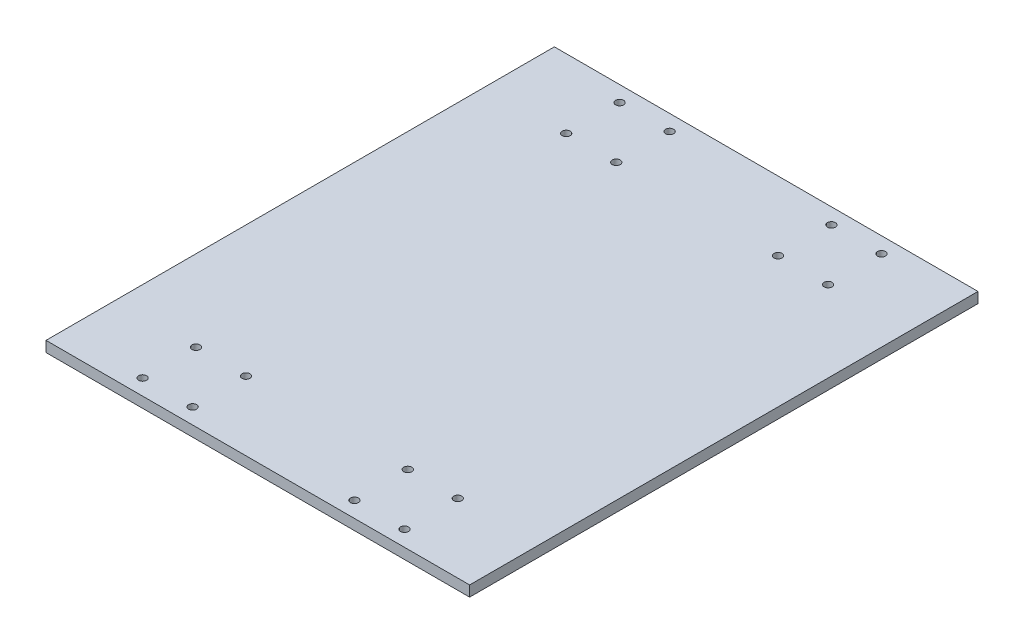
SolidWorks part; units mm, degrees
ref_plane "Front Plane" through (0, 0, 0) normal (0, 0, 1) x (1, 0, 0)
ref_plane "Top Plane" through (0, 0, 0) normal (0, 1, 0) x (1, 0, 0)
ref_plane "Right Plane" through (0, 0, 0) normal (1, 0, 0) x (0, 0, -1)
sketch "Sketch2" plane through (0, 0, 0) normal (0, 1, 0) x (1, 0, 0)
  line L1 (-127, 152.4) -> (127, 152.4)
  line L2 (-127, 152.4) -> (-127, -152.4)
  line L3 (-127, -152.4) -> (127, -152.4)
  line L4 (127, 152.4) -> (127, -152.4)
  line L5 (-127, 152.4) -> (127, -152.4) construction
  line L6 (-127, -152.4) -> (127, 152.4) construction
  point P0 (0, 0)
  dimension "D1" = 304.8
  dimension "D2" = 254
extrude "Boss-Extrude1" add sketch "Sketch2" along normal blind 6.35
ref_plane "Top" through (0, 0, -152.4) normal (0, 0, -1) x (-1, 0, 0)
hole_wizard "M4 Clearance Hole1" positions "Sketch4" profile "Sketch5" hole size "M4" standard "ANSI Metric" end condition up to next
sketch "Sketch4" plane through (0, 6.35, 0) normal (0, 1, 0) x (1, 0, 0)
  circle A0 centre (78.5, -111) radius 2.5 construction
  circle A1 centre (48.5, -111) radius 2.5 construction
  circle A2 centre (48.5, -143) radius 2.5 construction
  circle A3 centre (78.5, -143) radius 2.5 construction
  circle A4 centre (-48.5, -111) radius 2.5 construction
  circle A5 centre (-48.5, -143) radius 2.5 construction
  circle A6 centre (-78.5, -111) radius 2.5 construction
  circle A7 centre (-78.5, -143) radius 2.5 construction
  circle A8 centre (78.5, 143) radius 2.5 construction
  circle A9 centre (78.5, 111) radius 2.5 construction
  circle A10 centre (48.5, 143) radius 2.5 construction
  circle A11 centre (48.5, 111) radius 2.5 construction
  circle A12 centre (-48.5, 143) radius 2.5 construction
  circle A13 centre (-48.5, 111) radius 2.5 construction
  circle A14 centre (-78.5, 143) radius 2.5 construction
  circle A15 centre (-78.5, 111) radius 2.5 construction
  circle A16 centre (78.5, -111) radius 2.5 construction
  circle A17 centre (48.5, -111) radius 2.5 construction
  circle A18 centre (48.5, -143) radius 2.5 construction
  circle A19 centre (78.5, -143) radius 2.5 construction
  circle A20 centre (-48.5, -111) radius 2.5 construction
  circle A21 centre (-48.5, -143) radius 2.5 construction
  circle A22 centre (-78.5, -111) radius 2.5 construction
  circle A23 centre (-78.5, -143) radius 2.5 construction
  circle A24 centre (78.5, 143) radius 2.5 construction
  circle A25 centre (78.5, 111) radius 2.5 construction
  circle A26 centre (48.5, 143) radius 2.5 construction
  circle A27 centre (48.5, 111) radius 2.5 construction
  circle A28 centre (-48.5, 143) radius 2.5 construction
  circle A29 centre (-48.5, 111) radius 2.5 construction
  circle A30 centre (-78.5, 143) radius 2.5 construction
  circle A31 centre (-78.5, 111) radius 2.5 construction
  point P1 (78.5, -111)
  point P3 (48.5, -111)
  point P5 (48.5, -143)
  point P7 (78.5, -143)
  point P9 (-48.5, -111)
  point P11 (-48.5, -143)
  point P13 (-78.5, -111)
  point P15 (-78.5, -143)
  point P17 (78.5, 143)
  point P19 (78.5, 111)
  point P21 (48.5, 143)
  point P23 (48.5, 111)
  point P25 (-48.5, 143)
  point P27 (-48.5, 111)
  point P29 (-78.5, 143)
  point P31 (-78.5, 111)
sketch "Sketch5" plane through (78.5, 6.35, 111) normal (1, 0, 0) x (0, 0, 1)
  line L0 (0, 0) -> (0, 6.35)
  line L1 (0, 6.35) -> (2.4, 6.35)
  line L2 (2.4, 6.35) -> (2.4, 0)
  line L5 (2.4, 0) -> (0, 0)
  line L11 (0, -6.35) -> (0, 107.95) construction
  dimension "Thru Hole Dia." = 4.8
  dimension "Thru Hole Depth" = 6.35
